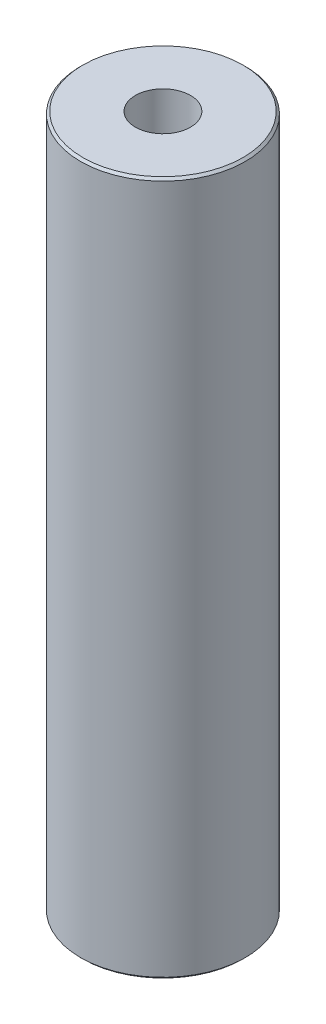
SolidWorks part; units mm, degrees
ref_plane "Front Plane" through (0, 0, 0) normal (0, 0, 1) x (1, 0, 0)
ref_plane "Top Plane" through (0, 0, 0) normal (0, 1, 0) x (1, 0, 0)
ref_plane "Right Plane" through (0, 0, 0) normal (1, 0, 0) x (0, 0, -1)
sketch "Sketch1" plane through (0, 0, 0) normal (0, 1, 0) x (1, 0, 0)
  circle A0 centre (0, 0) radius 55
  dimension "SHAFT_OD" = 110
extrude "Boss-Extrude1" add sketch "Sketch1" along normal blind 463.254
sketch "Sketch2" plane through (0, 0, 0) normal (0, 1, 0) x (1, 0, 0)
  circle A0 centre (0, 0) radius 18.3855
  dimension "BORE_D" = 36.7709
extrude "Cut-Extrude1" cut sketch "Sketch2" along normal through all
chamfer "Chamfer1" distance 1.5209 angle 45 2 edges at (0, 463.254, 55) (0, 0, 55)
